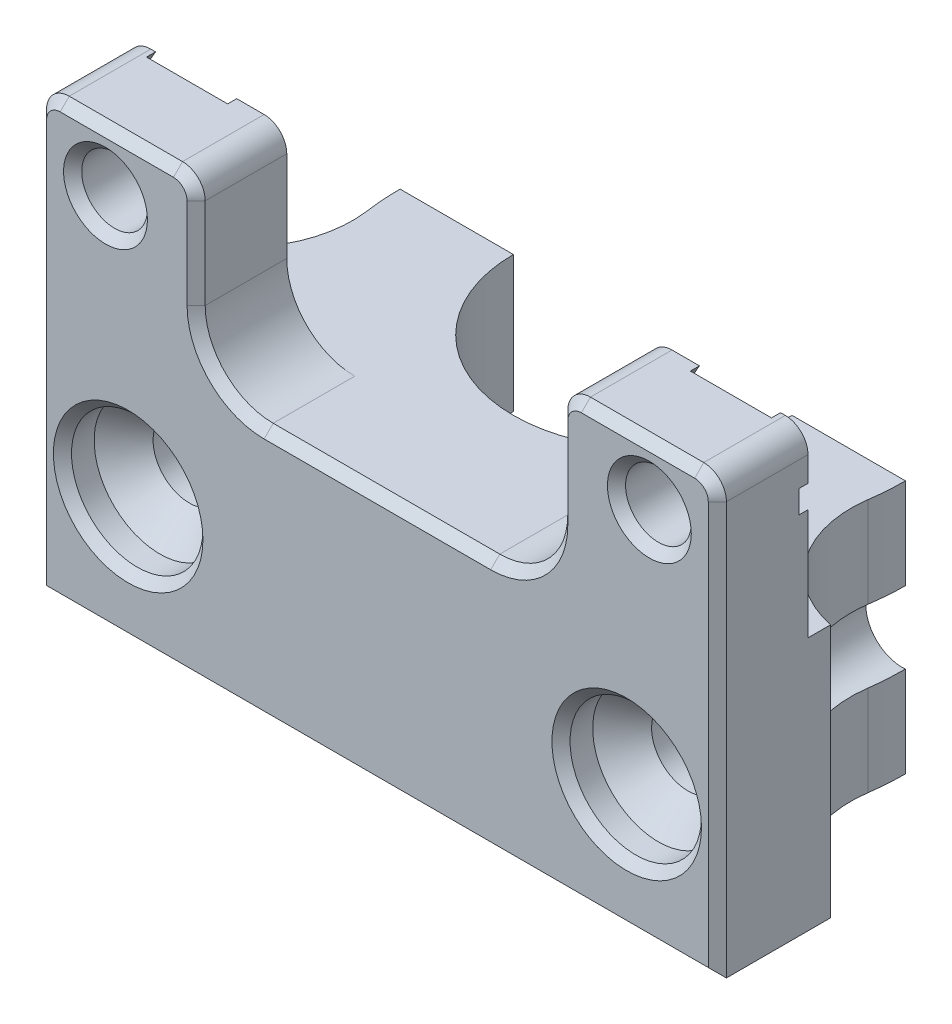
SolidWorks part; units mm, degrees
ref_plane "前视基准面" through (0, 0, 0) normal (0, 0, 1) x (1, 0, 0)
ref_plane "上视基准面" through (0, 0, 0) normal (0, 1, 0) x (1, 0, 0)
ref_plane "右视基准面" through (0, 0, 0) normal (1, 0, 0) x (0, 0, -1)
other "Configuration Table"
sketch "草图1" plane through (0, 0, 0) normal (0, 1, 0) x (1, 0, 0)
  line L0 (-11.15, 0) -> (-8.15, 0)
  line L1 (8.15, 0) -> (11.15, 0)
  arc A0 (-8.15, 0) -> (8.15, 0) centre (0, 0) ccw
  arc A1 (-11.15, 0) -> (11.15, 0) centre (0, 0) ccw
  circle A3 centre (0, 0) radius 11.15 construction
  circle A4 centre (0, 0) radius 8.15 construction
  point P4 (7.7939, 2.3828)
  point P7 (11.15, 0)
  dimension "D1" = 16.3
  dimension "D2" = 3
extrude "凸台-拉伸1" add sketch "草图1" along normal blind 5.2
sketch "草图2" plane through (0, 5.2, 0) normal (0, 1, 0) x (1, 0, 0)
  line L0 (-11.15, 0) -> (-6.15, 0)
  line L1 (6.15, 0) -> (11.15, 0)
  arc A0 (-11.15, 0) -> (11.15, 0) centre (0, 0) ccw
  arc A1 (-6.15, 0) -> (6.15, 0) centre (0, 0) ccw
  dimension "D1" = 12.3
extrude "凸台-拉伸2" add sketch "草图2" along normal blind 6
sketch "草图3" plane through (0, 11.2, 0) normal (0, 1, 0) x (1, 0, 0)
  line L0 (3.9115, -7.15) -> (15, -7.15)
  line L1 (-15, -7.15) -> (-3.9115, -7.15)
  line L2 (-15, -7.15) -> (-15, -11.15)
  line L3 (-15, -11.15) -> (15, -11.15)
  line L4 (15, -7.15) -> (15, -11.15)
  arc A0 (-11.15, 0) -> (11.15, 0) centre (0, 0) ccw construction
  arc A1 (-3.9115, -7.15) -> (3.9115, -7.15) centre (0, 0) ccw
  point P7 (0, -11.15)
  dimension "D1" = 11.15
  dimension "D2" = 30
  dimension "D3" = 0
  dimension "D4" = 4
extrude "凸台-拉伸3" add sketch "草图3" against normal up to surface (11.2 mm away) up to face at (0, 0, 4.825)
fillet "圆角1" radius 5 2 edges at (-8.5557, 5.6, 7.15) (8.5557, 5.6, 7.15)
sketch "草图4" plane through (0, 0, 11.15) normal (0, 0, 1) x (1, 0, 0)
  line L0 (-15, 0) -> (-15, 11.2) construction
  line L1 (15, 0) -> (15, 11.2) construction
  line L2 (-15, 11.2) -> (15, 11.2) construction
  circle A0 centre (-11, 5.6) radius 1.6
  circle A1 centre (11, 5.6) radius 1.6
  point P6 (-15, 5.6)
  point P9 (15, 5.6)
  point P12 (0, 11.2)
  dimension "D1" = 3.2
  dimension "D2" = 3.2
  dimension "D3" = 0
  dimension "D4" = 0
  dimension "D5" = 11
  dimension "D6" = 11
extrude "切除-拉伸1" cut sketch "草图4" against normal through all
sketch "草图7" plane through (0, 11.2, 0) normal (0, 1, 0) x (1, 0, 0)
  line L1 (-15, -11.15) -> (-8, -11.15)
  line L2 (-15, -11.15) -> (-15, -8.15)
  line L3 (-15, -8.15) -> (-8, -8.15)
  line L4 (-8, -11.15) -> (-8, -8.15)
  line L5 (15, -11.15) -> (8, -11.15)
  line L6 (15, -11.15) -> (15, -8.15)
  line L7 (15, -8.15) -> (8, -8.15)
  line L8 (8, -11.15) -> (8, -8.15)
  dimension "D1" = 3
  dimension "D2" = 3
  dimension "D3" = 7
  dimension "D4" = 7
extrude "凸台-拉伸5" add sketch "草图7" along normal blind 8
sketch "草图8" plane through (0, 0, 11.15) normal (0, 0, 1) x (1, 0, 0)
  line L0 (-15, 0) -> (-15, 19.2) construction
  circle A0 centre (-12, 16.6) radius 1.45
  circle A1 centre (12, 16.6) radius 1.45
  circle A2 centre (-11, 5.6) radius 1.6 construction
  circle A3 centre (11, 5.6) radius 1.6 construction
  dimension "D1" = 2.9
  dimension "D2" = 2.9
  dimension "D3" = 24
  dimension "D4" = 11
  dimension "D5" = 11
  dimension "D6" = 3
extrude "切除-拉伸3" cut sketch "草图8" against normal blind 8
sketch "草图9" plane through (0, 0, 11.15) normal (0, 0, 1) x (1, 0, 0)
  line L16 (-15, 19.2) -> (-15, 0)
  line L17 (-15, 0) -> (15, 0)
  line L18 (15, 0) -> (15, 19.2)
  line L19 (15, 19.2) -> (8, 19.2)
  line L20 (8, 19.2) -> (8, 11.2)
  line L21 (8, 11.2) -> (-8, 11.2)
  line L22 (-8, 11.2) -> (-8, 19.2)
  line L23 (-8, 19.2) -> (-15, 19.2)
  line L24 (-15, 19.2) -> (-15, 0)
  line L25 (-15, 0) -> (15, 0)
  line L26 (15, 0) -> (15, 19.2)
  line L27 (15, 19.2) -> (8, 19.2)
  line L28 (8, 19.2) -> (8, 11.2)
  line L29 (8, 11.2) -> (-8, 11.2)
  line L30 (-8, 11.2) -> (-8, 19.2)
  line L31 (-8, 19.2) -> (-15, 19.2)
  circle A0 centre (-12, 16.6) radius 1.45
  circle A1 centre (-11, 5.6) radius 1.6
  circle A2 centre (11, 5.6) radius 1.6
  circle A3 centre (12, 16.6) radius 1.45
  dimension "D1" = 0
extrude "凸台-拉伸6" add sketch "草图9" along normal blind 1
fillet "圆角2" radius 3 2 edges at (8, 11.2, 10.15) (-8, 11.2, 10.15)
fillet "圆角3" radius 1 4 edges at (15, 19.2, 10.15) (8, 19.2, 10.15) (-8, 19.2, 10.15) (-15, 19.2, 10.15)
sketch "草图10" plane through (0, 0, 12.15) normal (0, 0, 1) x (1, 0, 0)
  circle A0 centre (-11, 5.6) radius 2.9
  circle A1 centre (11, 5.6) radius 2.9
  dimension "D1" = 5.8
  dimension "D2" = 5.8
extrude "切除-拉伸4" cut sketch "草图10" against normal blind 2.7
chamfer "倒角2" distance 1.3 angle 45 2 edges at (-8.1, 5.6, 9.45) (13.9, 5.6, 9.45)
chamfer "倒角1" distance 0.4 angle 45 18 edges at (13.45, 16.6, 12.15) (0, 0, 12.15) (-15, 9.1, 12.15) (-14.7071, 18.9071, 12.15) (-11.5, 19.2, 12.15) (-8.2929, 18.9071, 12.15) (-8, 16.2, 12.15) (-7.1213, 12.0787, 12.15) (0, 11.2, 12.15) (7.1213, 12.0787, 12.15) (8, 16.2, 12.15) (8.2929, 18.9071, 12.15) (11.5, 19.2, 12.15) (14.7071, 18.9071, 12.15) (15, 9.1, 12.15) (-10.55, 16.6, 12.15) (13.9, 5.6, 12.15) (-8.1, 5.6, 12.15)
sketch "草图11" plane through (0, 0, 8.15) normal (0, 0, -1) x (-1, 0, 0)
  line L1 (-8.7091, 16.6) -> (-10.3546, 19.45)
  line L2 (-10.3546, 19.45) -> (-13.6454, 19.45)
  line L3 (-13.6454, 19.45) -> (-15.2909, 16.6)
  line L4 (-15.2909, 16.6) -> (-13.6454, 13.75)
  line L5 (-13.6454, 13.75) -> (-10.3546, 13.75)
  line L6 (-10.3546, 13.75) -> (-8.7091, 16.6)
  line L7 (15.2909, 16.6) -> (13.6454, 19.45)
  line L8 (13.6454, 19.45) -> (10.3546, 19.45)
  line L9 (10.3546, 19.45) -> (8.7091, 16.6)
  line L10 (8.7091, 16.6) -> (10.3546, 13.75)
  line L11 (10.3546, 13.75) -> (13.6454, 13.75)
  line L12 (13.6454, 13.75) -> (15.2909, 16.6)
  circle A0 centre (-12, 16.6) radius 2.85 construction
  circle A1 centre (12, 16.6) radius 2.85 construction
  dimension "D1" = 5.7
  dimension "D2" = 5.7
extrude "切除-拉伸5" cut sketch "草图11" against normal blind 0.4
equation "\"D1@草图3\"=22.3/2"
equation "\"D5@草图8\"=\"D4@草图8\""
